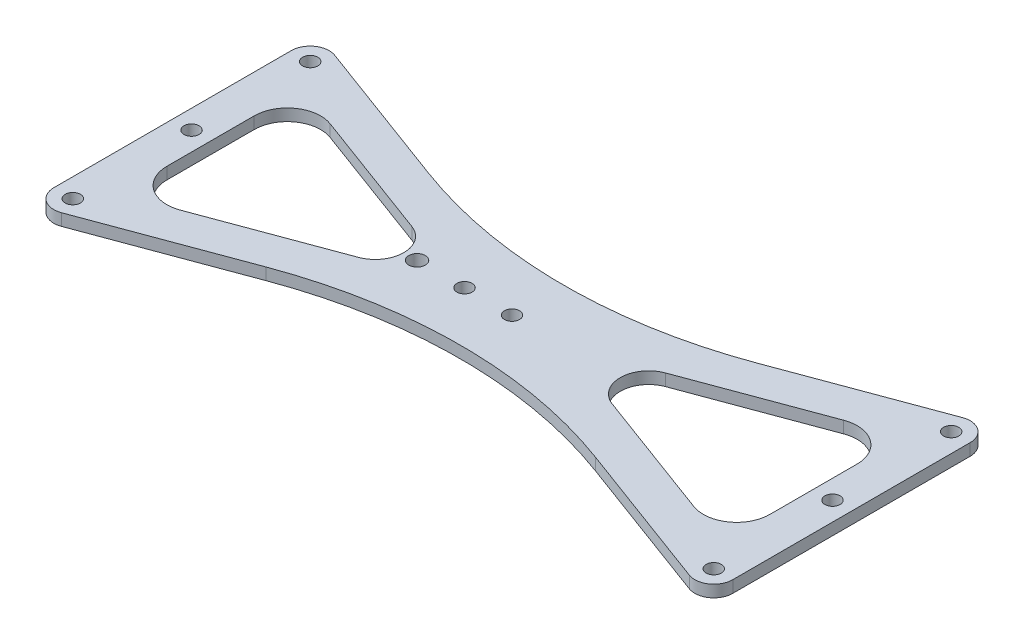
SolidWorks part; units mm, degrees
ref_plane "Front Plane" through (0, 0, 0) normal (0, 0, 1) x (1, 0, 0)
ref_plane "Top Plane" through (0, 0, 0) normal (0, 1, 0) x (1, 0, 0)
ref_plane "Right Plane" through (0, 0, 0) normal (1, 0, 0) x (0, 0, -1)
sketch "Sketch1" plane through (0, 0, 0) normal (0, 1, 0) x (1, 0, 0)
  line L0 (-85.725, 31.75) -> (85.725, -31.75) construction
  line L1 (85.725, 31.75) -> (-85.725, -31.75) construction
  line L2 (-85.725, 31.75) -> (-85.725, -31.75) construction
  line L3 (85.725, 31.75) -> (85.725, -31.75) construction
  line L4 (87.4894, 26.9862) -> (-83.9606, -36.5138)
  line L5 (-83.9606, 36.5138) -> (87.4894, -26.9862)
  line L6 (83.9606, 36.5138) -> (-87.4894, -26.9862)
  line L7 (-87.4894, 26.9862) -> (83.9606, -36.5138)
  line L8 (-90.805, 31.75) -> (-90.805, -31.75)
  line L9 (-80.645, 31.75) -> (-80.645, -31.75)
  line L10 (80.645, 31.75) -> (80.645, -31.75)
  line L11 (90.805, 31.75) -> (90.805, -31.75)
  line L12 (0, 0) -> (-25.4, 0) construction
  circle A0 centre (-85.725, -31.75) radius 2.032
  circle A1 centre (-85.725, 31.75) radius 2.032
  circle A2 centre (-85.725, 0) radius 2.032
  circle A3 centre (85.725, 31.75) radius 2.032
  circle A4 centre (85.725, 0) radius 2.032
  circle A5 centre (85.725, -31.75) radius 2.032
  arc A6 (87.4894, 26.9862) -> (83.9606, 36.5138) centre (85.725, 31.75) ccw
  arc A7 (-83.9606, -36.5138) -> (-87.4894, -26.9862) centre (-85.725, -31.75) cw
  arc A8 (-83.9606, 36.5138) -> (-87.4894, 26.9862) centre (-85.725, 31.75) ccw
  arc A9 (87.4894, -26.9862) -> (83.9606, -36.5138) centre (85.725, -31.75) cw
  arc A10 (-90.805, 31.75) -> (-80.645, 31.75) centre (-85.725, 31.75) cw
  arc A11 (-90.805, -31.75) -> (-80.645, -31.75) centre (-85.725, -31.75) ccw
  arc A12 (80.645, 31.75) -> (90.805, 31.75) centre (85.725, 31.75) cw
  arc A13 (80.645, -31.75) -> (90.805, -31.75) centre (85.725, -31.75) ccw
  circle A14 centre (0, 0) radius 2.032
  circle A15 centre (-12.7, 0) radius 2.032
  circle A16 centre (-25.4, 0) radius 2.2225
  point P4 (0, 0)
  point P8 (0, 0)
  point P34 (-12.7, 0)
  dimension "D3" = 4.064
  dimension "D10" = 4.064
  dimension "D13" = 4.445
  dimension "D1" = 63.5
  dimension "D2" = 171.45
  dimension "D11" = 12.7
  dimension "D12" = 12.7
  dimension "D4" = 5.08
  dimension "D5" = 5.08
  dimension "D6" = 5.08
  dimension "D7" = 5.08
  dimension "D8" = 5.08
  dimension "D9" = 5.08
extrude "Boss-Extrude1" add sketch "Sketch1" along normal blind 3.175 contours A7 A11 L9 L6 A0 | A8 L8 A7 L6 L9 L7 A2 | A11 L4 L7 L6 L9 | A10 A8 L7 L9 A1 | L5 A10 L9 L7 L6 | A13 L10 L5 L4 L7 | L6 L7 L4 L5 | L10 A12 L6 L5 L4 | L5 A9 L11 A6 L4 L10 A4 | A12 L10 L4 A6 A3 | L10 A13 A9 L5 A5 | L6 A15 L7 | L6 A15 L7 | L7 A15 L6 | A14 region at (90.4223, 0, -28.4806) region at (84.0116, 0, -25.8689) region at (43.9644, 0, -16.476) region at (43.9644, 0, 16.476) region at (7.2162, 0, 2.4466) region at (84.0116, 0, 25.8689) region at (-44.1127, 0, 16.5496) region at (-44.1127, 0, -16.5496) region at (-88.5355, 0, 35.7881) region at (-13.1268, 0, 1.1582) region at (-12.0893, 0, 0) region at (-81.6869, 0, -34.5605) region at (-13.1268, 0, -1.1582) region at (-90.1619, 0, 0) region at (0, 0, 0)
fillet "Fillet1" radius 8.89 4 edges at (-80.645, 1.5875, 24.4513) (-80.645, 1.5875, -24.4513) (80.645, 1.5875, 24.4513) (80.645, 1.5875, -24.4513)
fillet "Fillet2" radius 7.62 2 edges at (14.6265, 1.5875, 0) (-14.6265, 1.5875, 0)
fillet "Fillet3" radius 127 2 edges at (0, 1.5875, 5.4172) (0, 1.5875, -5.4172)
extrude "Cut-Extrude1" cut sketch "Sketch1<3>" along normal through all contours A16 | A15 | A14
sketch "Sketch1<3>" plane through (0, 0, 0) normal (0, 1, 0) x (1, 0, 0) same geometry as "Sketch1"
